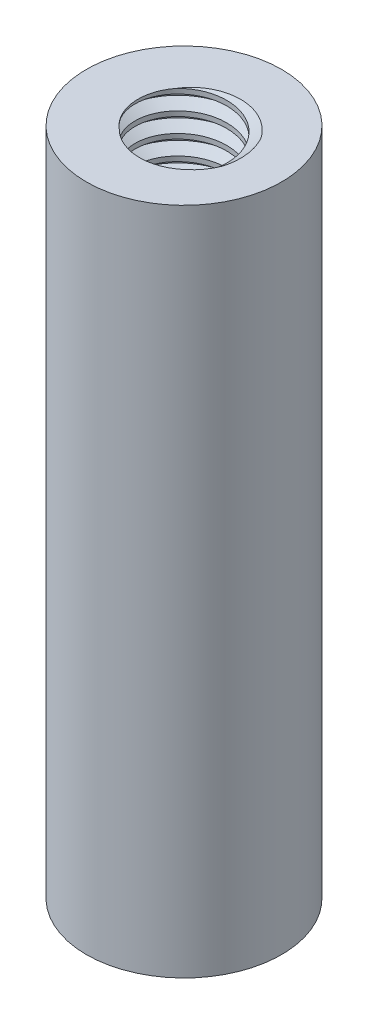
SolidWorks part; units mm, degrees
ref_plane "Front Plane" through (0, 0, 0) normal (0, 0, 1) x (1, 0, 0)
ref_plane "Top Plane" through (0, 0, 0) normal (0, 1, 0) x (1, 0, 0)
ref_plane "Right Plane" through (0, 0, 0) normal (1, 0, 0) x (0, 0, -1)
sketch "Sketch1" plane through (0, 0, 0) normal (0, 1, 0) x (1, 0, 0)
  circle A0 centre (0, 0) radius 3.5
  dimension "D1" = 7
extrude "Boss-Extrude1" add sketch "Sketch1" along normal mid plane 24
sketch "Sketch2" plane through (0, 12, 0) normal (0, 1, 0) x (1, 0, 0)
  circle A0 centre (0, 0) radius 1.65
  dimension "D1" = 3.3
extrude "Cut-Extrude1" cut sketch "Sketch2" against normal blind 6.5
thread "Thread1" pitch 0.7 method cut profile "Thread Profile1" start angle 0, offset 2, length 8, pitch 0.7, diameter 3.3
ref_plane "Plane1" through (-1.65, 14, 0) normal (0, 0, 1) x (-1, 0, 0)
sketch "Thread Profile1" plane through (-1.65, 14, 0) normal (0, 0, 1) x (-1, 0, 0)
  line L0 (0, 0) -> (0, 0.7) construction
  line L1 (0, 0) -> (0.3789, 0.2187)
  line L2 (0.3789, 0.2187) -> (0.3789, 0.3062)
  line L3 (0.3789, 0.3062) -> (0, 0.525)
  line L4 (0.3789, 0.2625) -> (0, 0.2625) construction
  line L11 (0, 0) -> (0, 0.525)
  point P2 (0, 0)
  dimension "Pitch" = 0.7
  dimension "Profile_Angle" = 60
  dimension "Profile_Land" = 0.0875
  dimension "Profile_Height" = 0.3789
mirror "Mirror3" about plane through (0, 0, 0) normal (0, 1, 0) of "Cut-Extrude1"
thread "Thread2" pitch 0.7 method cut profile "Thread Profile2" start angle 0, offset 2, length 8, pitch 0.7, diameter 3.3
ref_plane "Plane2" through (1.65, -14, 0) normal (0, 0, 1) x (1, 0, 0)
sketch "Thread Profile2" plane through (1.65, -14, 0) normal (0, 0, 1) x (1, 0, 0)
  line L0 (0, 0) -> (0, 0.7) construction
  line L1 (0, 0) -> (0.3789, 0.2187)
  line L2 (0.3789, 0.2187) -> (0.3789, 0.3062)
  line L3 (0.3789, 0.3062) -> (0, 0.525)
  line L4 (0.3789, 0.2625) -> (0, 0.2625) construction
  line L11 (0, 0) -> (0, 0.525)
  point P2 (0, 0)
  dimension "Pitch" = 0.7
  dimension "Profile_Angle" = 60
  dimension "Profile_Land" = 0.0875
  dimension "Profile_Height" = 0.3789
